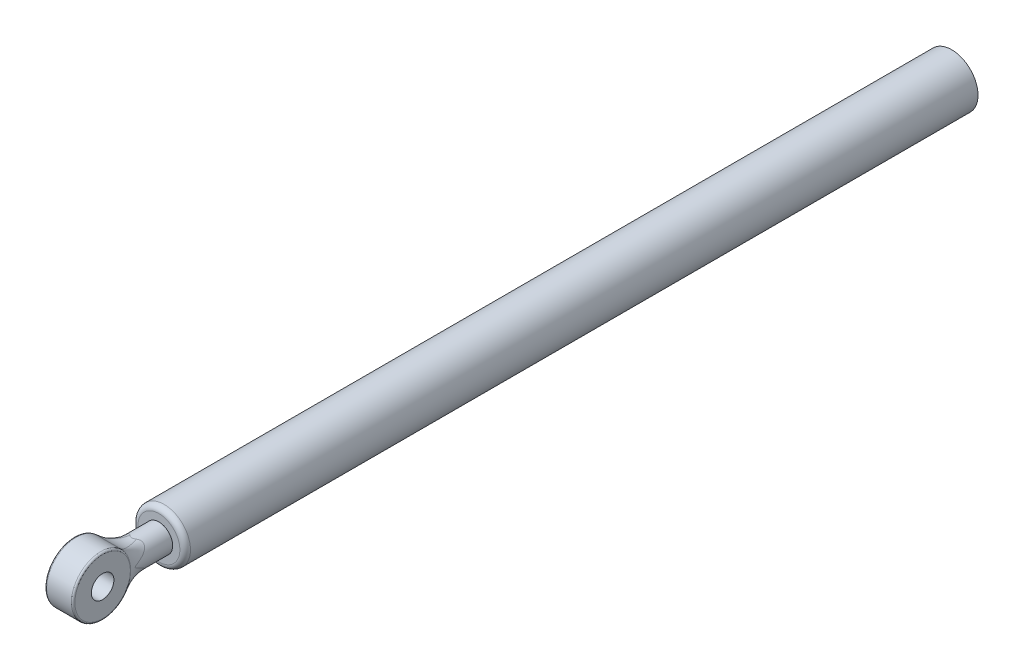
SolidWorks part; units mm, degrees
ref_plane "Alzado" through (0, 0, 0) normal (0, 0, 1) x (1, 0, 0)
ref_plane "Planta" through (0, 0, 0) normal (0, 1, 0) x (1, 0, 0)
ref_plane "Vista lateral" through (0, 0, 0) normal (1, 0, 0) x (0, 0, -1)
sketch "Croquis1" plane through (0, 0, 0) normal (0, 0, 1) x (1, 0, 0)
  circle A0 centre (0, 0) radius 14.9
extrude "Saliente-Extruir1" add sketch "Croquis1" along normal blind 450
sketch "Croquis2" plane through (0, 0, 450) normal (0, 0, 1) x (1, 0, 0)
  circle A0 centre (0, 0) radius 7.8
extrude "Saliente-Extruir2" add sketch "Croquis2" along normal blind 23.2
sketch "Croquis3" plane through (0, 0, 0) normal (1, 0, 0) x (0, 0, -1)
  line L0 (-473.2, 0) -> (-506.7, 0) construction
  line L1 (-473.2, 7.8) -> (-473.2, -7.8) construction
  circle A0 centre (-489.95, 0) radius 16.75
extrude "Saliente-Extruir5" add sketch "Croquis3" along normal blind 8 and the other way blind 8 separate body
sketch "Croquis5" plane through (8, 0, 0) normal (1, 0, 0) x (0, 0, -1)
  line L0 (-489.95, 16.75) -> (-489.95, -16.75) construction
  circle A0 centre (-489.95, 0) radius 16.75 construction
  circle A1 centre (-489.95, 0) radius 6.4
extrude "Cortar-Extruir1" cut sketch "Croquis5" against normal blind 17
fillet "Redondeo1" radius 3 1 edges at (14.9, 0, 450) type face fillet first side face at (14.9, 0, 450) second side face at (7.8, 0, 450)
fillet "Redondeo3" radius 1 2 edges at (8, 0, 473.2) (-8, 0, 473.2)
sketch "Croquis6" plane through (0, 0, 473.2) normal (0, 0, 1) x (1, 0, 0)
  circle A0 centre (0, 0) radius 7.8
extrude "Saliente-Extruir6" add sketch "Croquis6" along normal blind 4
fillet "Redondeo5" radius 21 2 edges at (-0.6113, 7.776, 475.1144) (0.6113, -7.776, 475.1144) type face fillet first side face at (0, 0, 474.3412) second side face at (0, 0, 490.9072)
